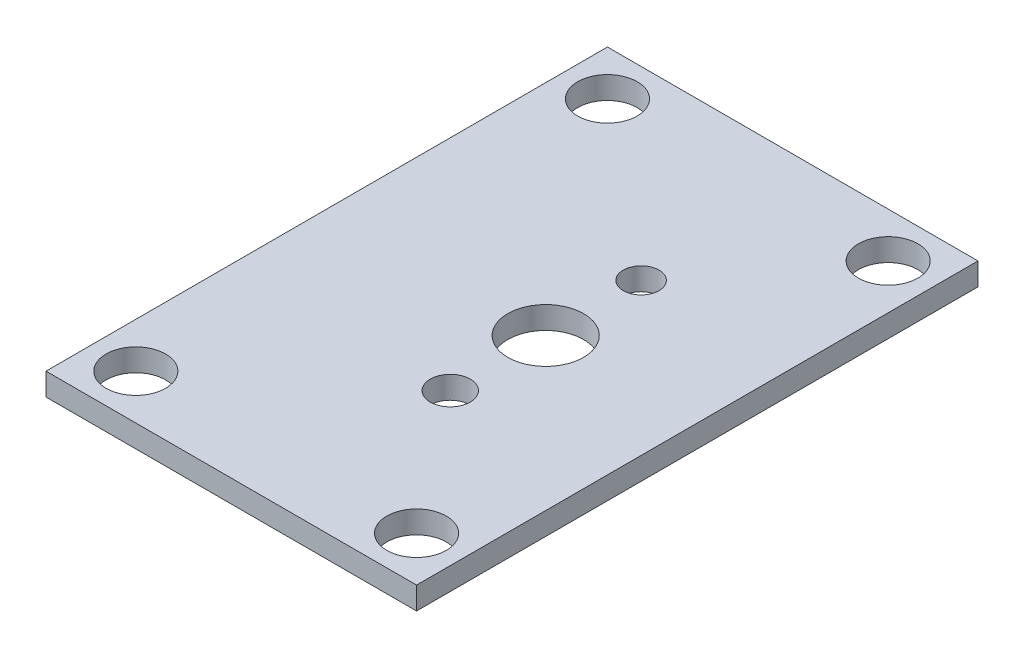
SolidWorks part; units mm, degrees
ref_plane "Front Plane" through (0, 0, 0) normal (0, 0, 1) x (1, 0, 0)
ref_plane "Top Plane" through (0, 0, 0) normal (0, 1, 0) x (1, 0, 0)
ref_plane "Right Plane" through (0, 0, 0) normal (1, 0, 0) x (0, 0, -1)
sketch "Sketch1" plane through (0, 0, 0) normal (0, 1, 0) x (1, 0, 0)
  line L1 (-10.223, 36.3848) -> (14.777, 36.3848)
  line L2 (-10.223, 36.3848) -> (-10.223, -13.6152)
  line L3 (-10.223, -13.6152) -> (14.777, -13.6152)
  line L4 (14.777, 36.3848) -> (14.777, -13.6152)
  circle A0 centre (1.277, 11.3848) radius 3.375
  dimension "D3" = 6.75
  dimension "D1" = 50
  dimension "D2" = 25
  dimension "D4" = 13.5
  dimension "D5" = 25
extrude "Boss-Extrude1" add sketch "Sketch1" along normal blind 2
sketch "Sketch2" plane through (-10.223, 0, 0) normal (-1, 0, 0) x (0, 0, 1)
  line L0 (55, 0) -> (-55, 0) construction
  line L1 (-36.3848, 2) -> (13.6152, 2)
  line L2 (-36.3848, 2) -> (-36.3848, 0)
  line L3 (-36.3848, 0) -> (13.6152, 0)
  line L4 (13.6152, 2) -> (13.6152, 0)
  line L5 (13.6152, 2) -> (13.6152, 0) construction
extrude "Boss-Extrude2" add sketch "Sketch2" along normal blind 8
sketch "Sketch3" plane through (0, 0, 0) normal (0, -1, 0) x (1, 0, 0)
  line L0 (-18.223, 13.6152) -> (14.777, 13.6152) construction
  line L1 (-18.223, -36.3848) -> (-10.223, -36.3848)
  line L2 (-18.223, -36.3848) -> (-18.223, 13.6152)
  line L3 (-18.223, 13.6152) -> (-10.223, 13.6152)
  line L4 (-10.223, -36.3848) -> (-10.223, 13.6152)
  dimension "D1" = 8
extrude "Boss-Extrude3" add sketch "Sketch3" along normal blind 42
sketch "Sketch4" plane through (0, 2, 0) normal (0, 1, 0) x (1, 0, 0)
  line L0 (-18.223, -13.6152) -> (-18.223, 36.3848) construction
  line L1 (14.777, 36.3848) -> (-18.223, 36.3848) construction
  line L2 (-18.223, -13.6152) -> (14.777, -13.6152) construction
  circle A0 centre (-14.223, 32.3848) radius 2.65
  circle A1 centre (-14.223, -9.6152) radius 2.65
  dimension "D2" = 5.3
  dimension "D4" = 5.3
  dimension "D5" = 4
  dimension "D6" = 4
  dimension "D1" = 4
  dimension "D3" = 4
extrude "Cut-Extrude1" cut sketch "Sketch4" against normal blind 3.3
ref_plane "Plane1" through (0, -20, 0) normal (0, 1, 0) x (1, 0, 0)
mirror "Mirror1" about plane through (0, -20, 0) normal (0, 1, 0) of "Cut-Extrude1"
sketch "Sketch5" plane through (-18.223, 0, 0) normal (-1, 0, 0) x (0, 0, 1)
  line L0 (55, 0) -> (-55, 0) construction
  line L1 (-6.9841, -24.1818) -> (-6.6547, -18.3888) construction
  line L2 (-6.6547, -18.3888) -> (-11.5069, -15.207) construction
  line L3 (-11.5069, -15.207) -> (-16.6885, -17.8182) construction
  line L4 (-16.6885, -17.8182) -> (-17.0179, -23.6112) construction
  line L5 (-17.0179, -23.6112) -> (-12.1657, -26.793) construction
  line L6 (-12.1657, -26.793) -> (-6.9841, -24.1818) construction
  circle A0 centre (-11.8363, -21) radius 5.025 construction
  circle A1 centre (-11.8363, -21) radius 5.8024
  dimension "D1" = 21
  dimension "D2" = 10.05
extrude "Cut-Extrude2" cut sketch "Sketch5" against normal blind 9
fillet "Fillet2" radius 1 1 edges at (-10.223, -21, -6.0339)
ref_plane "Plane2" through (-1.723, 0, 0) normal (-1, 0, 0) x (0, 0, 1)
mirror "Mirror2" about plane through (-1.723, 0, 0) normal (-1, 0, 0) of "Cut-Extrude1"
sketch "Sketch6" plane through (0, 2, 0) normal (0, 1, 0) x (1, 0, 0)
  line L0 (1.277, 14.7598) -> (1.277, 8.0098) construction
  line L1 (14.777, -13.6152) -> (14.777, 36.3848) construction
  line L2 (14.777, 17.202) -> (14.777, 5.5675)
  circle A0 centre (1.277, 11.3848) radius 3.375 construction
  circle A1 centre (1.277, 11.3848) radius 3.1
  circle A2 centre (1.277, 11.3848) radius 12.7
  arc A3 (14.777, 17.202) -> (14.777, 5.5675) centre (1.277, 11.3848) ccw
  line M9 (14.777, -13.6152) -> (14.777, 36.3848)
  dimension "D1" = 25.4
  dimension "D2" = 2
extrude "Boss-Extrude4" add sketch "Sketch6" along normal blind 2 contours A3 A2 M9
fillet "Fillet4" radius 1 1 edges at (14.777, 4, -11.3848)
sketch "Sketch8" plane through (0, 2, 0) normal (0, 1, 0) x (1, 0, 0)
  line L0 (4.652, 11.3848) -> (-2.098, 11.3848) construction
  circle A0 centre (1.277, 11.3848) radius 3.375 construction
  circle A1 centre (1.277, 19.8848) radius 1.5898
  circle A2 centre (1.277, 2.8848) radius 1.7774
  point P9 (1.277, 11.3848)
  dimension "D1" = 8.5
  dimension "D2" = 8.5
extrude "Cut-Extrude3" cut sketch "Sketch8" against normal blind 10
sketch "Sketch9" plane through (0, 0, 13.6152) normal (0, 0, 1) x (1, 0, 0)
  line L0 (-18.223, -42) -> (-18.223, 2) construction
  line L1 (-18.223, 0) -> (-10.223, 0)
  line L2 (-18.223, 0) -> (-18.223, -42)
  line L3 (-18.223, -42) -> (-10.223, -42)
  line L4 (-10.223, 0) -> (-10.223, -42)
extrude "Cut-Extrude4" cut sketch "Sketch9" against normal through all
ref_plane "Plane3" through (0, 0, 13.6152) normal (0, 0, 1) x (1, 0, 0)
sketch "Sketch10" plane through (0, 0, 13.6152) normal (0, 0, 1) x (1, 0, 0)
  line L1 (-18.223, 2) -> (15.2949, 2)
  line L2 (-18.223, 2) -> (-18.223, 9.2123)
  line L3 (-18.223, 9.2123) -> (15.2949, 9.2123)
  line L4 (15.2949, 2) -> (15.2949, 9.2123)
extrude "Cut-Extrude5" cut sketch "Sketch10" against normal blind 55
